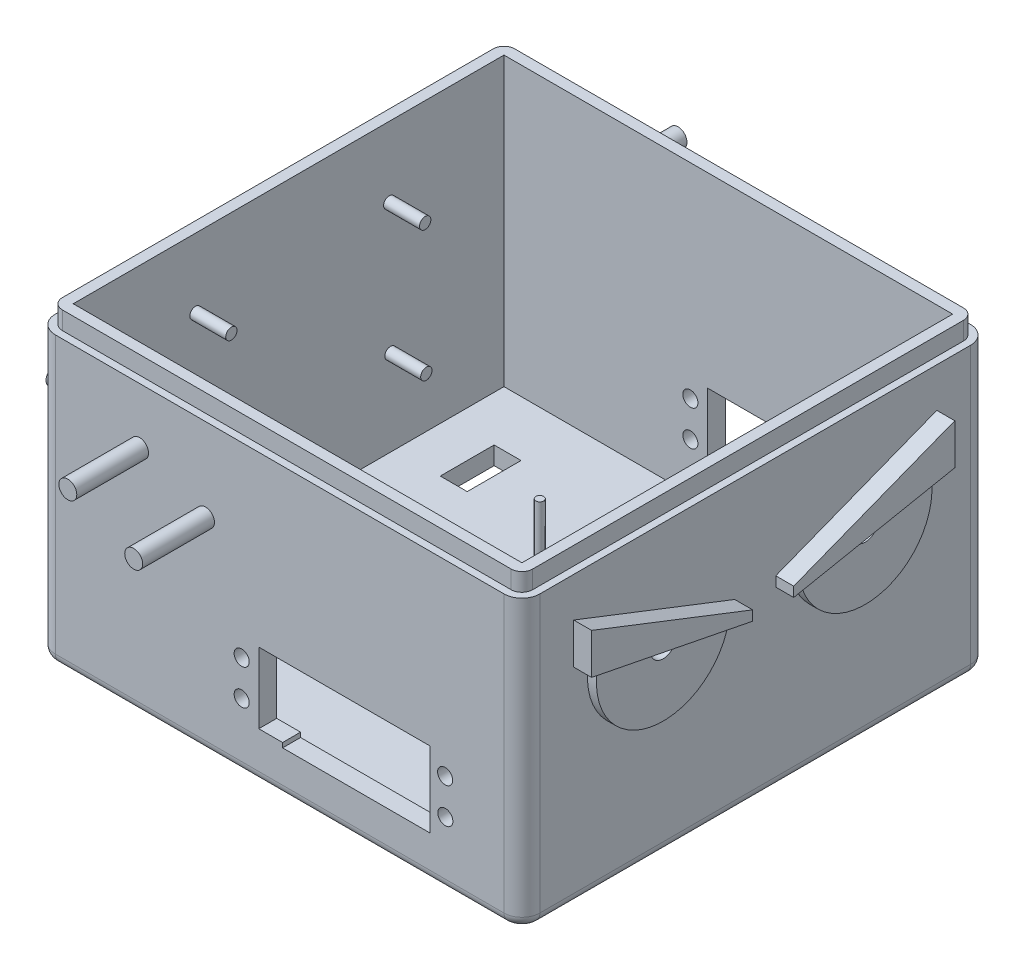
SolidWorks part; units mm, degrees
ref_plane "Front Plane" through (0, 0, 0) normal (0, 0, 1) x (1, 0, 0)
ref_plane "Top Plane" through (0, 0, 0) normal (0, 1, 0) x (1, 0, 0)
ref_plane "Right Plane" through (0, 0, 0) normal (1, 0, 0) x (0, 0, -1)
sketch "Sketch1" plane through (0, 0, 0) normal (0, 1, 0) x (1, 0, 0)
  line L1 (-65.9091, 67.1106) -> (69.0909, 67.1106)
  line L2 (-65.9091, 67.1106) -> (-65.9091, -62.8894)
  line L3 (-65.9091, -62.8894) -> (69.0909, -62.8894)
  line L4 (69.0909, 67.1106) -> (69.0909, -62.8894)
  dimension "D1" = 135
  dimension "D2" = 130
extrude "Boss-Extrude1" add sketch "Sketch1" along normal blind 80
fillet "Fillet3" radius 5 4 edges at (69.0909, 40, 62.8894) (-65.9091, 40, 62.8894) (69.0909, 40, -67.1106) (-65.9091, 40, -67.1106)
sketch "Sketch6" plane through (0, 80, 0) normal (0, 1, 0) x (1, 0, 0)
  line L8 (-60.9091, -60.8894) -> (64.0909, -60.8894)
  line L9 (67.0909, -57.8894) -> (67.0909, 62.1106)
  line L10 (64.0909, 65.1106) -> (-60.9091, 65.1106)
  line L11 (-63.9091, 62.1106) -> (-63.9091, -57.8894)
  line L12 (-60.9091, -60.8894) -> (64.0909, -60.8894)
  line L13 (67.0909, -57.8894) -> (67.0909, 62.1106)
  line L14 (64.0909, 65.1106) -> (-60.9091, 65.1106)
  line L15 (-63.9091, 62.1106) -> (-63.9091, -57.8894)
  arc A8 (64.0909, -60.8894) -> (67.0909, -57.8894) centre (64.0909, -57.8894) ccw
  arc A9 (67.0909, 62.1106) -> (64.0909, 65.1106) centre (64.0909, 62.1106) ccw
  arc A10 (-60.9091, 65.1106) -> (-63.9091, 62.1106) centre (-60.9091, 62.1106) ccw
  arc A11 (-63.9091, -57.8894) -> (-60.9091, -60.8894) centre (-60.9091, -57.8894) ccw
  arc A12 (64.0909, -60.8894) -> (67.0909, -57.8894) centre (64.0909, -57.8894) ccw
  arc A13 (67.0909, 62.1106) -> (64.0909, 65.1106) centre (64.0909, 62.1106) ccw
  arc A14 (-60.9091, 65.1106) -> (-63.9091, 62.1106) centre (-60.9091, 62.1106) ccw
  arc A15 (-63.9091, -57.8894) -> (-60.9091, -60.8894) centre (-60.9091, -57.8894) ccw
  dimension "D1" = 2
sketch "Sketch10" plane through (0, 80, 0) normal (0, 1, 0) x (1, 0, 0)
  line L8 (-60.9091, -60.8894) -> (64.0909, -60.8894)
  line L9 (67.0909, -57.8894) -> (67.0909, 62.1106)
  line L10 (64.0909, 65.1106) -> (-60.9091, 65.1106)
  line L11 (-63.9091, 62.1106) -> (-63.9091, -57.8894)
  line L12 (-60.9091, -60.8894) -> (64.0909, -60.8894)
  line L13 (67.0909, -57.8894) -> (67.0909, 62.1106)
  line L14 (64.0909, 65.1106) -> (-60.9091, 65.1106)
  line L15 (-63.9091, 62.1106) -> (-63.9091, -57.8894)
  arc A8 (64.0909, -60.8894) -> (67.0909, -57.8894) centre (64.0909, -57.8894) ccw
  arc A9 (67.0909, 62.1106) -> (64.0909, 65.1106) centre (64.0909, 62.1106) ccw
  arc A10 (-60.9091, 65.1106) -> (-63.9091, 62.1106) centre (-60.9091, 62.1106) ccw
  arc A11 (-63.9091, -57.8894) -> (-60.9091, -60.8894) centre (-60.9091, -57.8894) ccw
  arc A12 (64.0909, -60.8894) -> (67.0909, -57.8894) centre (64.0909, -57.8894) ccw
  arc A13 (67.0909, 62.1106) -> (64.0909, 65.1106) centre (64.0909, 62.1106) ccw
  arc A14 (-60.9091, 65.1106) -> (-63.9091, 62.1106) centre (-60.9091, 62.1106) ccw
  arc A15 (-63.9091, -57.8894) -> (-60.9091, -60.8894) centre (-60.9091, -57.8894) ccw
  dimension "D1" = 2
shell "Shell4" thickness 5 removed face at (1.5909, 80, -2.1106)
extrude "Boss-Extrude5" add sketch "Sketch6" along normal blind 5 contours L12 A12 L13 A13 L14 A14 L15 A15
sketch "Sketch12" plane through (0, 85, 0) normal (0, 1, 0) x (1, 0, 0)
  line L1 (-60.9091, 62.1106) -> (64.0909, 62.1106)
  line L2 (-60.9091, 62.1106) -> (-60.9091, -57.8894)
  line L3 (-60.9091, -57.8894) -> (64.0909, -57.8894)
  line L4 (64.0909, 62.1106) -> (64.0909, -57.8894)
extrude "Cut-Extrude7" cut sketch "Sketch12" against normal blind 30
sketch "Sketch51" plane through (0, 0, 62.8894) normal (0, 0, 1) x (1, 0, 0)
  line L0 (-4.2231, 13.3069) -> (35.6769, 13.3069)
  line L1 (-10.2731, 13.3069) -> (-3.9231, 13.3069) construction
  line L2 (35.3769, 13.3069) -> (41.7269, 13.3069) construction
  line L3 (35.6769, 13.3069) -> (35.6769, 33.0069)
  line L4 (41.7269, 33.0069) -> (35.3769, 33.0069) construction
  line L5 (35.6769, 33.0069) -> (-4.2231, 33.0069)
  line L6 (-3.9231, 33.0069) -> (-10.2731, 33.0069) construction
  line L7 (-4.2231, 33.0069) -> (-4.2231, 13.3069)
  circle A0 centre (-8.9842, 28.0819) radius 2.1
  circle A1 centre (-8.9842, 18.2319) radius 2.1
  circle A2 centre (40.4381, 28.0819) radius 2.1
  circle A3 centre (40.4381, 18.2319) radius 2.1
extrude "Cut-Extrude8" cut sketch "Sketch51" against normal through all
sketch "Sketch52" plane through (0, 0, 62.8894) normal (0, 0, 1) x (1, 0, 0)
  circle A0 centre (-37.4241, 64.4481) radius 2.5
extrude "Boss-Extrude29" add sketch "Sketch52" along normal blind 20
sketch "Sketch53" plane through (0, 0, -67.1106) normal (0, 0, -1) x (-1, 0, 0)
  circle A0 centre (37.4241, 64.4481) radius 2.5
extrude "Boss-Extrude30" add sketch "Sketch53" along normal blind 20
sketch "Sketch54" plane through (0, 5, 0) normal (0, 1, 0) x (1, 0, 0)
  circle A0 centre (-13.883, 25.0524) radius 1.0974
  circle A1 centre (37.009, 10.2612) radius 1.0974
  circle A2 centre (37.2525, -17.6466) radius 1.0974
  circle A3 centre (-14.7316, -23.1788) radius 1.0974
extrude "Boss-Extrude31" add sketch "Sketch54" along normal blind 15
sketch "Sketch55" plane through (0, 5, 0) normal (0, 1, 0) x (1, 0, 0)
  circle A0 centre (59.2809, 10.7461) radius 1.4936
  circle A1 centre (59.3811, -5.2536) radius 1.4936
extrude "Boss-Extrude32" add sketch "Sketch55" along normal blind 10
sketch "Sketch56" plane through (0, 5, 0) normal (0, 1, 0) x (1, 0, 0)
  circle A0 centre (54.8079, 1.1027) radius 2.9236
extrude "Boss-Extrude33" add sketch "Sketch56" along normal blind 5
sketch "Sketch58" plane through (-60.9091, 0, 0) normal (1, 0, 0) x (0, 0, -1)
  line L0 (30.4834, 28.9394) -> (30.4838, 28.9394) construction
  circle A0 centre (-23.8251, 65.7698) radius 1.5839
  circle A1 centre (30.1595, 65.4552) radius 1.5839
  circle A2 centre (30.4838, 28.9394) radius 1.5838
  circle A3 centre (-23.4941, 28.4604) radius 1.5837
extrude "Boss-Extrude35" add sketch "Sketch58" along normal blind 10
sketch "Sketch60" plane through (0, 5, 0) normal (0, 1, 0) x (1, 0, 0)
  line L1 (-47.6443, -23.8115) -> (-40.1443, -23.8115)
  line L2 (-47.6443, -23.8115) -> (-47.6443, -38.8115)
  line L3 (-47.6443, -38.8115) -> (-40.1443, -38.8115)
  line L4 (-40.1443, -23.8115) -> (-40.1443, -38.8115)
  line L5 (-48.2107, 31.665) -> (-40.7107, 31.665)
  line L6 (-48.2107, 31.665) -> (-48.2107, 46.665)
  line L7 (-48.2107, 46.665) -> (-40.7107, 46.665)
  line L8 (-40.7107, 31.665) -> (-40.7107, 46.665)
extrude "Cut-Extrude10" cut sketch "Sketch60" against normal blind 10
sketch "Sketch61" plane through (-65.9091, 0, 0) normal (-1, 0, 0) x (0, 0, 1)
  circle A0 centre (26.4206, 32.4255) radius 8
extrude "Boss-Extrude36" add sketch "Sketch61" along normal blind 5
sketch "Sketch62" plane through (-65.9091, 0, 0) normal (-1, 0, 0) x (0, 0, 1)
  circle A0 centre (2.9794, 50.2865) radius 2.5
  circle A1 centre (42.9794, 50.2865) radius 2.5
  circle A2 centre (41.9153, 10.8641) radius 2.5
  circle A3 centre (2.9794, 10.441) radius 2.5
extrude "Boss-Extrude37" add sketch "Sketch62" along normal blind 15
sketch "Sketch64" plane through (69.0909, 0, 0) normal (1, 0, 0) x (0, 0, -1)
  line L0 (-48.4736, 68.9828) -> (-48.4736, 57.627)
  line L1 (-48.4736, 57.627) -> (-3.6089, 48.7697)
  line L2 (-3.6089, 48.7697) -> (-3.6089, 51.5069)
  line L3 (-3.6089, 51.5069) -> (-48.4736, 68.9828)
sketch "Sketch66" plane through (69.0909, 0, 0) normal (1, 0, 0) x (0, 0, -1)
  line L0 (-48.4736, 57.627) -> (-3.6089, 48.7697) construction
  line L1 (-44.2704, 56.7972) -> (-7.8121, 49.5995)
  arc A0 (-44.2704, 56.7972) -> (-7.8121, 49.5995) centre (-26.0413, 53.1984) ccw
extrude "Boss-Extrude38" add sketch "Sketch66" along normal blind 2.5
extrude "Boss-Extrude39" add sketch "Sketch64" along normal blind 5
ref_plane "Plane1" through (0, 0, -2.1106) normal (0, 0, 1) x (1, 0, 0)
sketch "Sketch69" plane through (69.0909, 0, 0) normal (1, 0, 0) x (0, 0, -1)
  line L0 (-48.4736, 57.627) -> (-3.6089, 48.7697) construction
  line L1 (-29.5133, 53.8838) -> (-22.5692, 52.5129)
  arc A0 (-29.5133, 53.8838) -> (-22.5692, 52.5129) centre (-26.0413, 53.1984) ccw
extrude "Cut-Extrude11" cut sketch "Sketch69" along normal blind 5
mirror "Mirror3" about plane through (0, 0, -2.1106) normal (0, 0, 1) of "Cut-Extrude11", "Boss-Extrude38", "Boss-Extrude39"
fillet "Fillet4" radius 3 8 edges at (-64.4446, 0, -65.6462) (67.6264, 0, -65.6462) (67.6264, 0, 61.4249) (-64.4446, 0, 61.4249) (1.5909, 0, -67.1106) (69.0909, 0, -2.1106) (1.5909, 0, 62.8894) (-65.9091, 0, -2.1106)
sketch "Sketch14" plane through (0, 0, -67.1106) normal (0, 0, -1) x (-1, 0, 0)
  line L1 (-43.4159, 33.0069) -> (-2.4159, 33.0069)
  line L2 (-43.4159, 33.0069) -> (-43.4159, 12.0069)
  line L3 (-43.4159, 12.0069) -> (-2.4159, 12.0069)
  line L4 (-2.4159, 33.0069) -> (-2.4159, 12.0069)
  dimension "D1" = 41
  dimension "D2" = 21
extrude "Cut-Extrude5" cut sketch "Sketch14" against normal through all both and the other way through all
sketch "Sketch38" plane through (0, 0, 62.8894) normal (0, 0, 1) x (1, 0, 0)
  circle A0 centre (-19.0644, 56.8929) radius 2.5
extrude "Boss-Extrude19" add sketch "Sketch38" along normal blind 20
sketch "Sketch39" plane through (0, 0, 62.8894) normal (0, 0, 1) x (1, 0, 0)
  circle A0 centre (47.6985, 27.838) radius 2.0999
  circle A1 centre (47.754, 17.9882) radius 2.0999
  circle A2 centre (-1.6663, 17.7115) radius 2.1
  circle A3 centre (-1.7045, 27.5709) radius 2.0999
extrude "Cut-Extrude6" cut sketch "Sketch39" against normal through all
sketch "Sketch40" plane through (0, 0, -67.1106) normal (0, 0, -1) x (-1, 0, 0)
  circle A0 centre (19.0644, 56.8929) radius 2.5
extrude "Boss-Extrude20" add sketch "Sketch40" along normal blind 20
sketch "Sketch41" plane through (-65.9091, 0, 0) normal (-1, 0, 0) x (0, 0, 1)
  circle A0 centre (-52.5045, 59.7587) radius 1.7433
  circle A1 centre (15.529, 62.7908) radius 1.7433
  circle A2 centre (-15.2045, 18.7587) radius 1.7433
  circle A3 centre (-52.5045, 18.7587) radius 1.7433
extrude "Boss-Extrude21" add sketch "Sketch41" along normal blind 10
sketch "Sketch42" plane through (-60.9091, 0, 0) normal (1, 0, 0) x (0, 0, -1)
  line L0 (30.4834, 28.9394) -> (30.4838, 28.9394) construction
  circle A0 centre (30.1595, 65.4552) radius 1.5839
  circle A1 centre (30.4838, 28.9394) radius 1.5838
  circle A2 centre (-23.4941, 28.4604) radius 1.5837
  circle A3 centre (-23.8251, 65.7698) radius 1.5839
extrude "Boss-Extrude22" add sketch "Sketch42" along normal blind 10
sketch "Sketch43" plane through (0, 5, 0) normal (0, 1, 0) x (1, 0, 0)
  circle A0 centre (-13.883, 25.0524) radius 1.0974
  circle A1 centre (37.009, 10.2612) radius 1.0974
  circle A2 centre (37.2525, -17.6466) radius 1.0974
  circle A3 centre (-14.7316, -23.1788) radius 1.0974
extrude "Boss-Extrude23" add sketch "Sketch43" along normal blind 15
sketch "Sketch48" plane through (0, 5, 0) normal (0, 1, 0) x (1, 0, 0)
  circle A0 centre (57.2555, 0.9128) radius 2.8916
extrude "Boss-Extrude27" add sketch "Sketch48" along normal blind 5
sketch "Sketch49" plane through (0, 5, 0) normal (0, 1, 0) x (1, 0, 0)
  circle A0 centre (59.2809, 10.7461) radius 1.4936
  circle A1 centre (59.3811, -5.2536) radius 1.4936
extrude "Boss-Extrude28" add sketch "Sketch49" along normal blind 10
